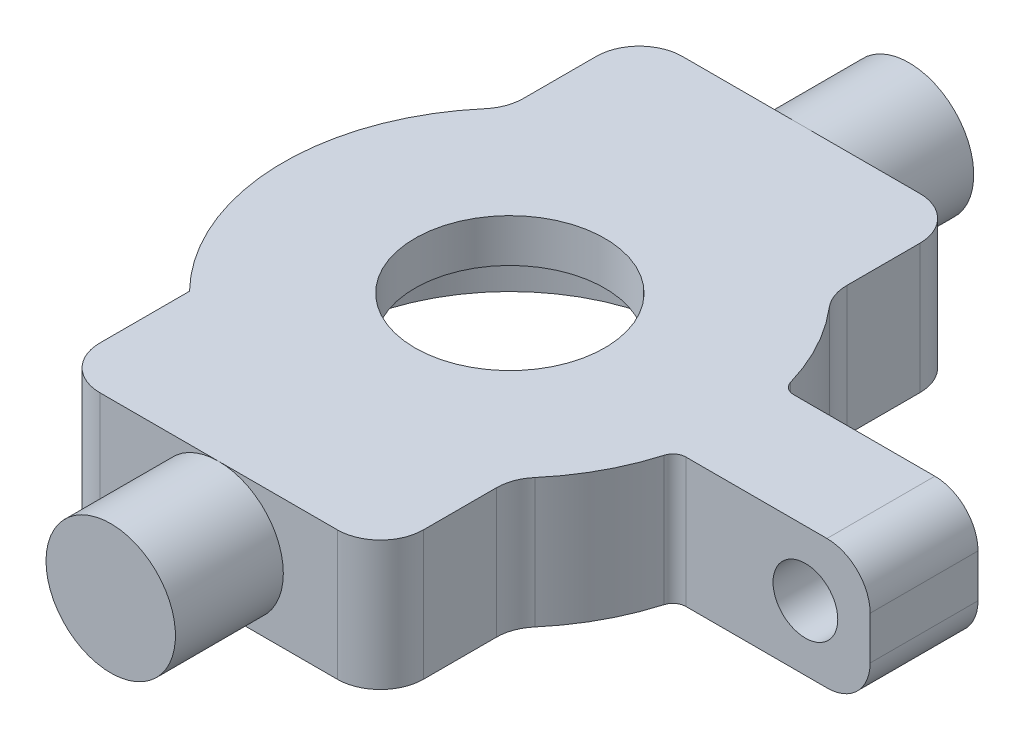
SolidWorks part; units mm, degrees
ref_plane "Front Plane" through (0, 0, 0) normal (0, 0, 1) x (1, 0, 0)
ref_plane "Top Plane" through (0, 0, 0) normal (0, 1, 0) x (1, 0, 0)
ref_plane "Right Plane" through (0, 0, 0) normal (1, 0, 0) x (0, 0, -1)
sketch "Sketch1" plane through (0, 0, 0) normal (0, 1, 0) x (1, 0, 0)
  line L0 (-7.5, 7.3485) -> (-7.5, 13.5)
  line L1 (-7.5, 13.5) -> (7.5, 13.5)
  line L2 (7.5, 13.5) -> (7.5, 7.3485)
  line L3 (0, 13.5) -> (0, 0) construction
  line L4 (0, 0) -> (10.5, 0) construction
  line L5 (-7.5, 13.5) -> (-7.5, 7.3485)
  line L6 (7.5, 7.3485) -> (7.5, 13.5)
  line L7 (7.5, -7.3485) -> (7.5, -13.5)
  line L8 (-7.5, -13.5) -> (-7.5, -7.3485)
  line L9 (7.5, -13.5) -> (7.5, -7.3485)
  line L10 (-7.5, -13.5) -> (7.5, -13.5)
  line L11 (-7.5, -7.3485) -> (-7.5, -13.5)
  circle A0 centre (0, 0) radius 10.5
  circle A1 centre (0, 0) radius 4.4
  dimension "D1" = 27
  dimension "D4" = 8.8
  dimension "D2" = 15
  dimension "D3" = 3
extrude "Boss-Extrude1" add sketch "Sketch1" along normal blind 6 contours A0 L2 L1 L0 | A0 L8 L10 L7 region at (0, 0, -11.4062) region at (0, 0, 11.4062)
extrude "Boss-Extrude2" add sketch "Sketch1<3>" along normal blind 2 contours A0 region at (0, 0, -10.203)
sketch "Sketch1<3>" plane through (0, 0, 0) normal (0, 1, 0) x (1, 0, 0) same geometry as "Sketch1"
sketch "Sketch2" plane through (0, 2, 0) normal (0, 1, 0) x (1, 0, 0)
  circle A0 centre (0, 0) radius 8.575
  arc A4 (7.5, 7.3485) -> (-7.5, 7.3485) centre (0, 0) ccw
  arc A5 (-7.5, 7.3485) -> (-7.5, -7.3485) centre (0, 0) ccw
  arc A6 (-7.5, -7.3485) -> (7.5, -7.3485) centre (0, 0) ccw
  arc A7 (7.5, -7.3485) -> (7.5, 7.3485) centre (0, 0) ccw
  arc A8 (7.5, 7.3485) -> (-7.5, 7.3485) centre (0, 0) ccw
  arc A9 (-7.5, 7.3485) -> (-7.5, -7.3485) centre (0, 0) ccw
  arc A10 (-7.5, -7.3485) -> (7.5, -7.3485) centre (0, 0) ccw
  arc A11 (7.5, -7.3485) -> (7.5, 7.3485) centre (0, 0) ccw
  dimension "D2" = 17.15
  dimension "D1" = 0
extrude "Boss-Extrude3" add sketch "Sketch2" along normal up to surface (4 mm away) up to face at (0, 6, -11.2121)
sketch "Sketch3" plane through (0, 0, -13.5) normal (0, 0, -1) x (-1, 0, 0)
  line L0 (10.5, 3) -> (-10.5, 3) construction
  line L1 (10.5, 0) -> (10.5, 6) construction
  line L2 (-10.5, 6) -> (-10.5, 0) construction
  circle A0 centre (0, 3) radius 3
  dimension "D1" = 6
extrude "Boss-Extrude4" add sketch "Sketch3" along normal blind 5
mirror "Mirror1" about plane through (0, 0, 0) normal (0, 0, 1) of "Boss-Extrude4"
sketch "Sketch4" plane through (0, 6, 0) normal (0, 1, 0) x (1, 0, 0)
  line L0 (0, 0) -> (10.198, 0) construction
  line L1 (10.198, -2.5) -> (19.198, -2.5)
  line L2 (10.198, -2.5) -> (10.198, 2.5) construction
  line L3 (10.198, 2.5) -> (19.198, 2.5)
  line L4 (19.198, -2.5) -> (19.198, 2.5)
  arc A0 (7.5, -7.3485) -> (7.5, 7.3485) centre (0, 0) ccw construction
  arc A1 (10.198, -2.5) -> (10.198, 2.5) centre (0, 0) ccw
  dimension "D1" = 9
  dimension "D2" = 5
extrude "Boss-Extrude5" add sketch "Sketch4" against normal up to surface (6 mm away) up to face at (0, 0, 0)
sketch "Sketch5" plane through (0, 0, -2.5) normal (0, 0, -1) x (-1, 0, 0)
  line L3 (-19.198, 0) -> (-19.198, 6) construction
  line L4 (-19.198, 3) -> (-10.198, 3) construction
  line L5 (-10.198, 0) -> (-10.198, 6) construction
  circle A2 centre (-16.198, 3) radius 1.5
  dimension "D1" = 3
  dimension "D2" = 3
extrude "Cut-Extrude1" cut sketch "Sketch5" against normal up to next
fillet "Fillet1" radius 2 9 edges at (-7.5, 3, -7.3485) (-7.5, 3, -13.5) (7.5, 3, -13.5) (7.5, 3, -7.3485) (7.5, 3, 7.3485) (-7.5, 3, 13.5) (7.5, 3, 13.5) (19.198, 0, 0) (19.198, 6, 0)
fillet "Fillet2" radius 0.6 2 edges at (10.198, 3, -2.5) (10.198, 3, 2.5)
ref_plane "Plane1" through (0, 16, 0) normal (0, 1, 0) x (1, 0, 0)
mirror "Mirror3" about plane through (0, 16, 0) normal (0, 1, 0) of bodies 110
delete or keep bodies "Body-Delete/Keep 1" type delete bodies bodies 110
